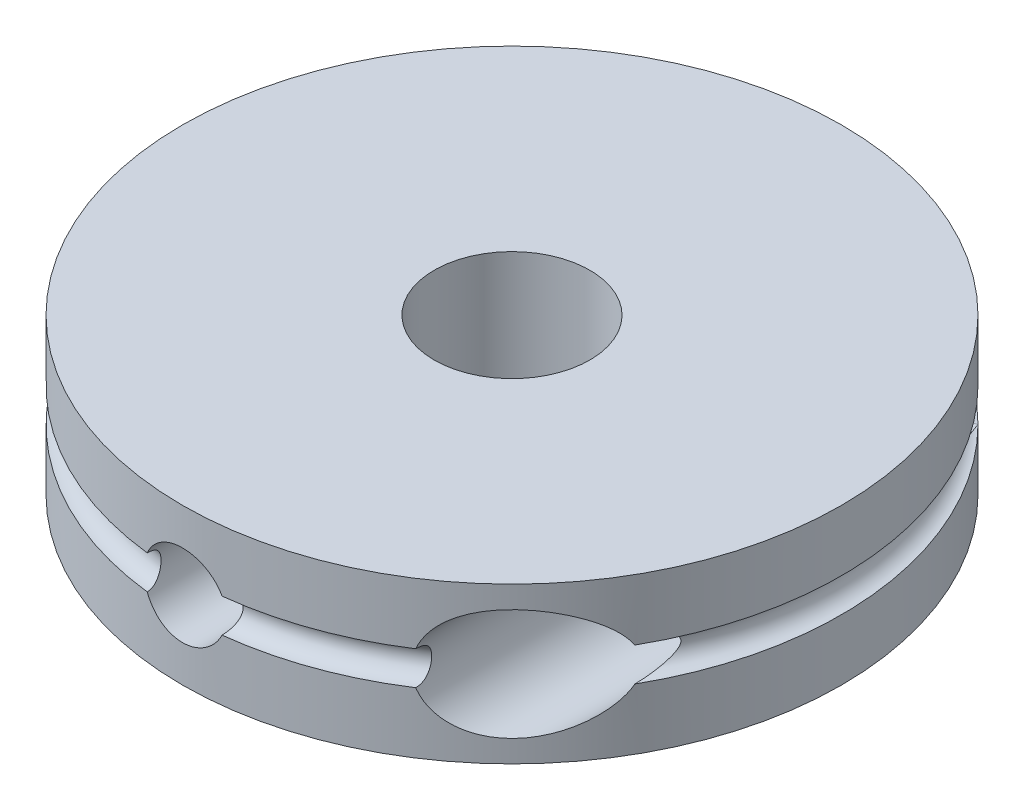
SolidWorks part; units mm, degrees
material "6063-T5"
ref_plane "Front Plane" through (0, 0, 0) normal (0, 0, 1) x (1, 0, 0)
ref_plane "Top Plane" through (0, 0, 0) normal (0, 1, 0) x (1, 0, 0)
ref_plane "Right Plane" through (0, 0, 0) normal (1, 0, 0) x (0, 0, -1)
sketch "BASE" plane through (0, 0, 0) normal (0, 1, 0) x (1, 0, 0)
  circle A0 centre (0, 0) radius 12.7
  circle A1 centre (0, 0) radius 3
  dimension "D1" = 25.4
  dimension "D2" = 6
extrude "MAIN_BODY" add sketch "BASE" along normal blind 6
sketch "Sketch4" plane through (0, 0, 0) normal (0, 0, 1) x (1, 0, 0)
  line L0 (12.7, 0) -> (12.7, 6) construction
  line L1 (0, 0) -> (0, 6) construction
  line L2 (-12.7, 0) -> (12.7, 0) construction
  line L3 (12.7, 6) -> (-12.7, 6) construction
  circle A0 centre (12.7, 3) radius 0.65
  dimension "D1" = 1.3
revolve "CABLE_GUIDE" cut sketch "Sketch4" angle 360 about L1
sketch "Sketch5" plane through (0, 0, 0) normal (0, 0, 1) x (1, 0, 0)
  line L0 (0, 3) -> (0, 0) construction
  circle A0 centre (0, 3) radius 1.5811
  dimension "D2" = 3.1623
  dimension "D1" = 3
extrude "Cut-Extrude2" cut sketch "Sketch5" along normal up to next
sketch "Sketch8" plane through (0, 0, 0) normal (0, 0, 1) x (1, 0, 0)
  line L0 (0, 3) -> (12.05, 3) construction
  arc A0 (12.7, 3.65) -> (12.7, 2.35) centre (12.7, 3) ccw construction
  circle A1 centre (8.9803, 3) radius 0.65
  dimension "D1" = 1.3
  dimension "D2" = 8.9803
extrude "Cut-Extrude3" cut sketch "Sketch8" against normal through all both and the other way through all
sketch "Sketch9" plane through (0, 0, 0) normal (0, 0, 1) x (1, 0, 0)
  circle A0 centre (8.9803, 3) radius 2.15
  dimension "D1" = 4.3
extrude "Cut-Extrude4" cut sketch "Sketch9" along normal through all
